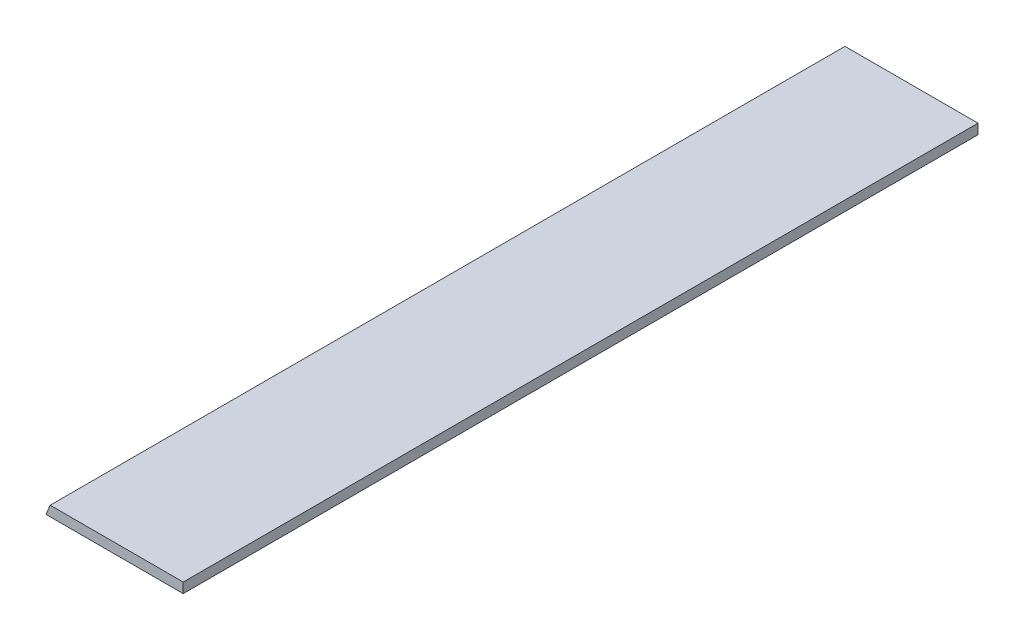
SolidWorks part; units mm, degrees
ref_plane "Front Plane" through (0, 0, 0) normal (0, 0, 1) x (1, 0, 0)
ref_plane "Top Plane" through (0, 0, 0) normal (0, 1, 0) x (1, 0, 0)
ref_plane "Right Plane" through (0, 0, 0) normal (1, 0, 0) x (0, 0, -1)
sketch "Sketch1" plane through (0, 0, 0) normal (0, 0, 1) x (1, 0, 0)
  line L0 (0, 0) -> (2.6303, 6.35)
  line L1 (2.6303, 6.35) -> (86.614, 6.35)
  line L2 (86.614, 6.35) -> (86.614, 0)
  line L3 (86.614, 0) -> (0, 0)
  dimension "D1" = 86.614
  dimension "D2" = 67.5
  dimension "D3" = 6.35
extrude "Boss-Extrude1" add sketch "Sketch1" along normal blind 501.65
